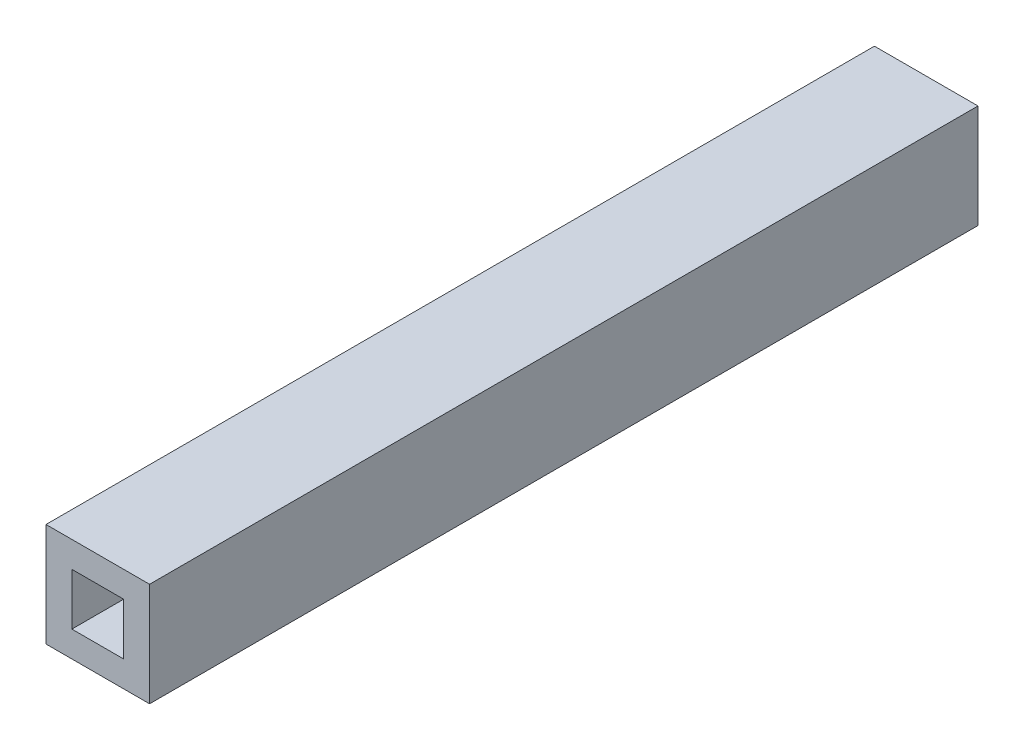
SolidWorks part; units mm, degrees
ref_plane "Front Plane" through (0, 0, 0) normal (0, 0, 1) x (1, 0, 0)
ref_plane "Top Plane" through (0, 0, 0) normal (0, 1, 0) x (1, 0, 0)
ref_plane "Right Plane" through (0, 0, 0) normal (1, 0, 0) x (0, 0, -1)
sketch "Sketch1" plane through (0, 0, 0) normal (0, 0, 1) x (1, 0, 0)
  line L1 (0, 0) -> (25.4, 0)
  line L2 (0, 0) -> (0, 25.4)
  line L3 (0, 25.4) -> (25.4, 25.4)
  line L4 (25.4, 0) -> (25.4, 25.4)
  dimension "D1" = 25.4
  dimension "D2" = 25.4
extrude "Boss-Extrude1" add sketch "Sketch1" along normal blind 203.2
sketch "Sketch2" plane through (0, 0, 203.2) normal (0, 0, 1) x (1, 0, 0)
  line L1 (6.35, 19.05) -> (19.05, 19.05)
  line L2 (6.35, 19.05) -> (6.35, 6.35)
  line L3 (6.35, 6.35) -> (19.05, 6.35)
  line L4 (19.05, 19.05) -> (19.05, 6.35)
  line L9 (25.4, 25.4) -> (0, 25.4) construction
  line L10 (0, 25.4) -> (0, 0) construction
  line L11 (0, 0) -> (25.4, 0) construction
  line L16 (25.4, 0) -> (25.4, 25.4) construction
  dimension "D1" = 6.35
  dimension "D2" = 6.35
  dimension "D3" = 6.35
  dimension "D4" = 6.35
extrude "Cut-Extrude1" cut sketch "Sketch2" against normal through all
